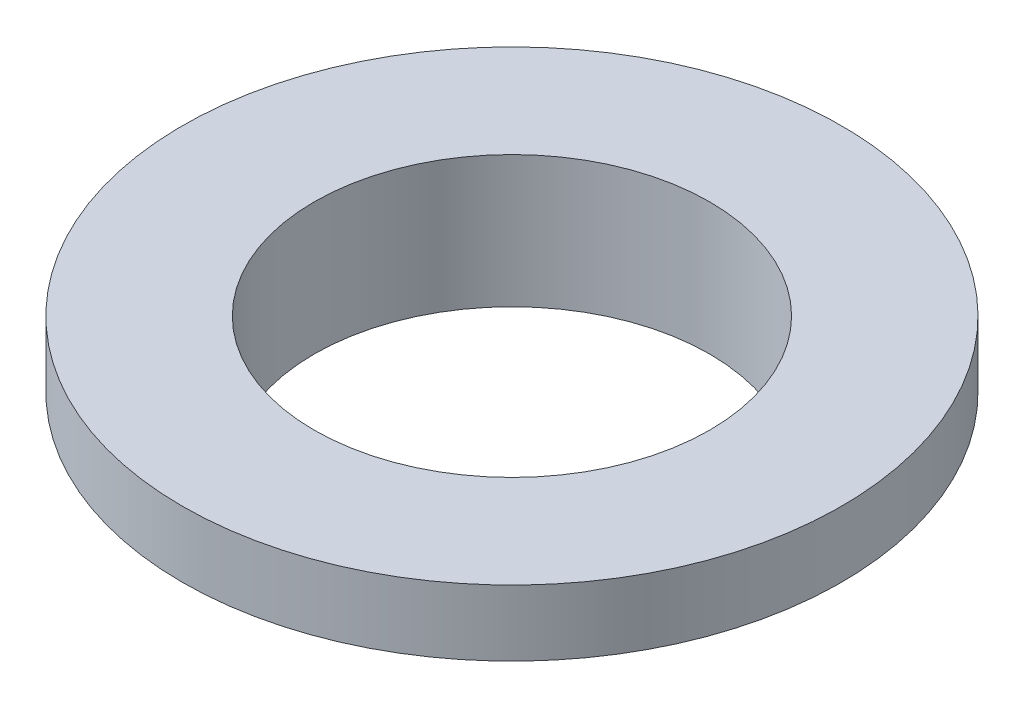
SolidWorks part; units mm, degrees
other "Markup1"
sketch "Sketch4" plane through (-50, -10.0045, -50) normal (-0.1255, -0.9677, -0.2187) x (0.9887, -0.1404, 0.0535)
sketch "Sketch5" plane through (-50, -10.0045, -50) normal (-0.1255, -0.9677, -0.2187) x (0.9887, -0.1404, 0.0535)
sketch "Sketch7" plane through (-50, -11.0131, -50) normal (-0.1255, -0.9677, -0.2187) x (0.9887, -0.1404, 0.0535)
ref_plane "Front Plane" through (0, 0, 0) normal (0, 0, 1) x (1, 0, 0)
ref_plane "Top Plane" through (0, 0, 0) normal (0, 1, 0) x (1, 0, 0)
ref_plane "Right Plane" through (0, 0, 0) normal (1, 0, 0) x (0, 0, -1)
sketch "Sketch1" plane through (0, 0, 0) normal (0, 1, 0) x (1, 0, 0)
  circle A0 centre (0, 0) radius 50
  circle A1 centre (0, 0) radius 30
  dimension "D1" = 100
  dimension "D2" = 60
extrude "Boss-Extrude1" add sketch "Sketch1" along normal blind 10
sketch "Sketch2" plane through (0, 0, 0) normal (0, -1, 0) x (1, 0, 0)
  circle A3 centre (0, 0) radius 32.45
  dimension "D1" = 64.9
extrude "Boss-Extrude2" add sketch "Sketch2" along normal blind 30
sketch "Sketch3" plane through (0, 0, 0) normal (0, 1, 0) x (1, 0, 0)
  circle A0 centre (0, 0) radius 30
extrude "Cut-Extrude1" cut sketch "Sketch3" against normal through all
thread "Thread1" pitch 3 method cut profile "Thread Profile1" start angle 0, offset 0, length 30, pitch 3, diameter 64.9
ref_plane "Plane1" through (32.45, -30, 0) normal (0, 0, 1) x (1, 0, 0)
sketch "Thread Profile1" plane through (32.45, -30, 0) normal (0, 0, 1) x (1, 0, 0)
  line L0 (0, 0) -> (0, 3) construction
  line L11 (0, 0) -> (0, 2.625)
  line L12 (0, 2.625) -> (-1.6238, 1.6875)
  line L13 (-1.6238, 1.6875) -> (-1.6238, 0.9375)
  line L15 (-1.6238, 0.9375) -> (0, 0)
  line L17 (-1.6238, 1.3125) -> (0, 1.3125) construction
  point P2 (0, 0)
  dimension "Pitch" = 3
  dimension "Profile_Angle" = 60
  dimension "Profile_Land" = 0.75
  dimension "Profile_Height" = 1.6238
sketch "Sketch6" plane through (0, 0, 0) normal (1, 0, 0) x (0, 0, -1)
  line L1 (-36.6926, -10) -> (35.2014, -10)
  line L2 (-36.6926, -10) -> (-36.6926, -32)
  line L3 (-36.6926, -32) -> (35.2014, -32)
  line L4 (35.2014, -10) -> (35.2014, -32)
  dimension "D1" = 10
  dimension "D2" = 22
extrude "Cut-Extrude2" cut sketch "Sketch6" against normal blind 50 and the other way blind 50
